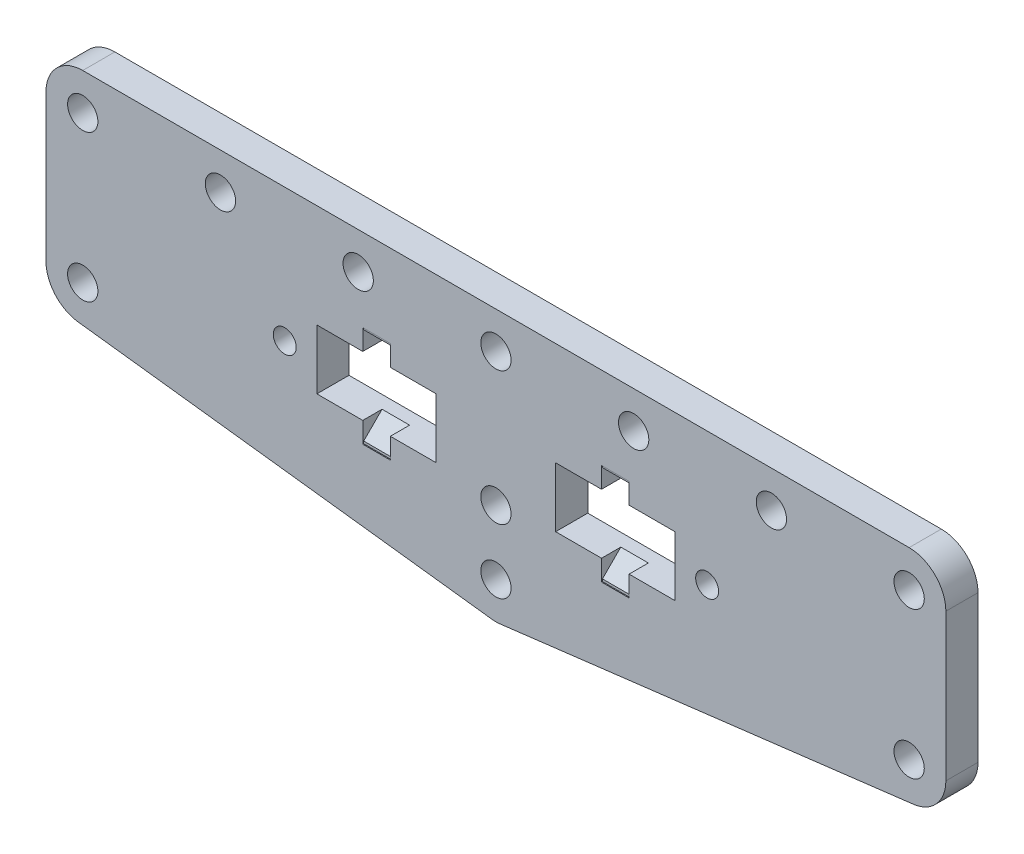
SolidWorks part; units mm, degrees
ref_plane "Płaszczyzna przednia" through (0, 0, 0) normal (0, 0, 1) x (1, 0, 0)
ref_plane "Płaszczyzna górna" through (0, 0, 0) normal (0, 1, 0) x (1, 0, 0)
ref_plane "Płaszczyzna prawa" through (0, 0, 0) normal (1, 0, 0) x (0, 0, -1)
sketch "Szkic1" plane through (0, 0, 0) normal (0, 0, 1) x (1, 0, 0)
  line L0 (0, 0) -> (60.5866, 0) construction
  line L1 (0.4853, -10.9705) -> (45.4853, -5.4705)
  line L2 (49, -1.5) -> (49, 14.5)
  line L3 (45, 18.5) -> (-45, 18.5)
  line L4 (0, 25.8414) -> (0, -26.3345) construction
  line L5 (-0.4853, -10.9705) -> (-45.4853, -5.4705)
  line L6 (-49, -1.5) -> (-49, 14.5)
  circle A0 centre (0, 0) radius 1.65
  circle A1 centre (0, -7) radius 1.65
  circle A2 centre (45, -1.5) radius 1.65
  circle A3 centre (45, 14.5) radius 1.65
  arc A4 (-0.4853, -10.9705) -> (0.4853, -10.9705) centre (0, -7) ccw
  arc A5 (45.4853, -5.4705) -> (48.7081, 0) centre (45, -1.5) ccw
  arc A6 (49, 14.5) -> (45, 18.5) centre (45, 14.5) ccw
  circle A7 centre (-45, -1.5) radius 1.65
  arc A8 (-45.4853, -5.4705) -> (-49, -1.5) centre (-45, -1.5) cw
  circle A9 centre (-45, 14.5) radius 1.65
  arc A10 (-49, 14.5) -> (-45, 18.5) centre (-45, 14.5) cw
  point P32 (0, 18.5)
  dimension "D1" = 3.3
  dimension "D2" = 3.3
  dimension "D5" = 3.3
  dimension "D7" = 3.3
  dimension "D9" = 8
  dimension "D10" = 8
  dimension "D3" = 7
  dimension "D4" = 1.5
  dimension "D6" = 45
  dimension "D8" = 16
extrude "Dodanie-wyciągnięcie1" add sketch "Szkic1" along normal blind 3.5 contours A10 L6 A8 L5 A4 L1 A5 L2 A6 L3 A7 A3 A2 A1 A0 A9 region at (0, 5.2024, 0)
sketch "Szkic2" plane through (0, 0, 3.5) normal (0, 0, 1) x (1, 0, 0)
  line L1 (6.5, 7.25) -> (19.5, 7.25)
  line L2 (6.5, 7.25) -> (6.5, 0.75)
  line L3 (6.5, 0.75) -> (19.5, 0.75)
  line L4 (19.5, 7.25) -> (19.5, 0.75)
  line L5 (6.5, 7.25) -> (19.5, 0.75) construction
  line L6 (6.5, 0.75) -> (19.5, 7.25) construction
  point P0 (13, 4)
  dimension "D1" = 13
  dimension "D2" = 13
  dimension "D3" = 6.5
  dimension "D4" = 4
extrude "Wytnij-wyciągnięcie1" cut sketch "Szkic2" against normal blind 4
sketch "Szkic3" plane through (0, 0, 3.5) normal (0, 0, 1) x (1, 0, 0)
  line L0 (19.5, 4) -> (28.4602, 4) construction
  line L1 (19.5, 0.75) -> (19.5, 7.25) construction
  line L2 (19.5, 7.25) -> (6.5, 7.25) construction
  circle A0 centre (23, 4) radius 1.25
  point P8 (13, 7.25)
  dimension "D1" = 2.5
  dimension "D2" = 10
extrude "Wytnij-wyciągnięcie2" cut sketch "Szkic3" against normal blind 4
mirror "Lustro1" about plane through (0, 0, 0) normal (1, 0, 0) of "Wytnij-wyciągnięcie1", "Wytnij-wyciągnięcie2"
sketch "Szkic4" plane through (0, 0, 3.5) normal (0, 0, 1) x (1, 0, 0)
  line L0 (-45, 14.5) -> (45, 14.5) construction
  circle A0 centre (0, 14.5) radius 1.65
  circle A1 centre (15, 14.5) radius 1.65
  circle A2 centre (30, 14.5) radius 1.65
  dimension "D1" = 3.3
  dimension "D2" = 3.3
  dimension "D3" = 3.3
  dimension "D4" = 15
  dimension "D5" = 15
extrude "Wytnij-wyciągnięcie3" cut sketch "Szkic4" against normal blind 4
mirror "Lustro2" about plane through (0, 0, 0) normal (1, 0, 0) of "Wytnij-wyciągnięcie3"
sketch "Szkic5" plane through (0, 0, 3.5) normal (0, 0, 1) x (1, 0, 0)
  line L0 (6.5, 4) -> (19.5, 4) construction
  line L1 (6.5, 7.25) -> (6.5, 0.75) construction
  line L2 (19.5, 0.75) -> (19.5, 7.25) construction
  line L3 (13, 7.25) -> (13, 0.75) construction
  line L4 (19.5, 7.25) -> (6.5, 7.25) construction
  line L5 (6.5, 0.75) -> (19.5, 0.75) construction
  line L7 (11.5, 9.5) -> (14.5, 9.5)
  line L8 (11.5, 9.5) -> (11.5, -1.5)
  line L9 (11.5, -1.5) -> (14.5, -1.5)
  line L10 (14.5, 9.5) -> (14.5, -1.5)
  line L11 (11.5, 9.5) -> (14.5, -1.5) construction
  line L12 (11.5, -1.5) -> (14.5, 9.5) construction
  point P12 (13, 4)
  dimension "D1" = 3
  dimension "D2" = 11
extrude "Wytnij-wyciągnięcie4" cut sketch "Szkic5" against normal blind 0.1
chamfer "Sfazowanie1" distance 2 angle 45 2 edges at (13, 0.75, 3.4) (13, 7.25, 3.4)
mirror "Lustro6" about plane through (0, 0, 0) normal (1, 0, 0) of "Wytnij-wyciągnięcie4"
chamfer "Sfazowanie2" distance 2 angle 45 2 edges at (-13, 0.75, 3.4) (-13, 7.25, 3.4)
